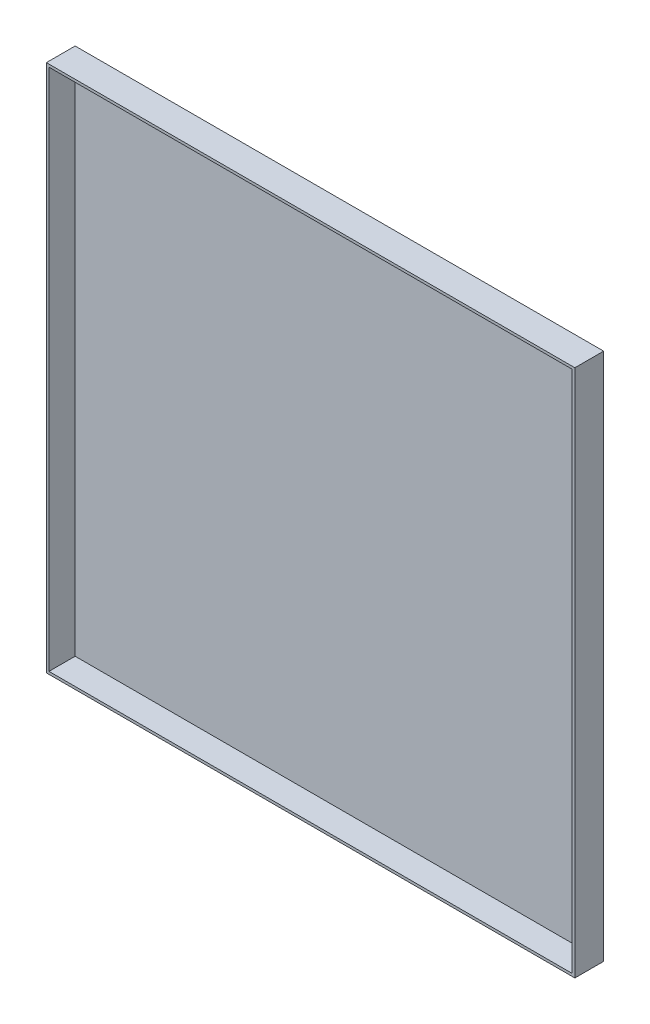
SolidWorks part; units mm, degrees
ref_plane "前视基准面" through (0, 0, 0) normal (0, 0, 1) x (1, 0, 0)
ref_plane "上视基准面" through (0, 0, 0) normal (0, 1, 0) x (1, 0, 0)
ref_plane "右视基准面" through (0, 0, 0) normal (1, 0, 0) x (0, 0, -1)
sketch "草图1" plane through (0, 0, 0) normal (0, 0, 1) x (1, 0, 0)
  line L1 (-13.9953, 188.5714) -> (186.0047, 188.5714)
  line L2 (-13.9953, 188.5714) -> (-13.9953, -11.4286)
  line L3 (-13.9953, -11.4286) -> (186.0047, -11.4286)
  line L4 (186.0047, 188.5714) -> (186.0047, -11.4286)
  dimension "D1" = 200
  dimension "D2" = 200
sketch "草图2" plane through (0, 0, 0) normal (0, 0, 1) x (1, 0, 0)
  line L0 (-13.9953, 188.5714) -> (186.0047, 188.5714) construction
  line L1 (-14.9953, 189.5714) -> (187.0047, 189.5714)
  line L2 (-14.9953, 189.5714) -> (-14.9953, -12.4286)
  line L3 (-14.9953, -12.4286) -> (187.0047, -12.4286)
  line L4 (187.0047, 189.5714) -> (187.0047, -12.4286)
  line L5 (-13.9953, 188.5714) -> (-13.9953, -11.4286) construction
  line L6 (-13.9953, -11.4286) -> (186.0047, -11.4286) construction
  line L7 (186.0047, 188.5714) -> (186.0047, -11.4286) construction
  dimension "D1" = 1
  dimension "D2" = 1
  dimension "D3" = 1
  dimension "D4" = 1
extrude "凸台-拉伸1" add sketch "草图2" against normal blind 11
extrude "凸台-拉伸2" add sketch "草图1" against normal blind 10 separate body
combine bodies "组合1" operation type subtract main body 101 bodies to subtract 102
